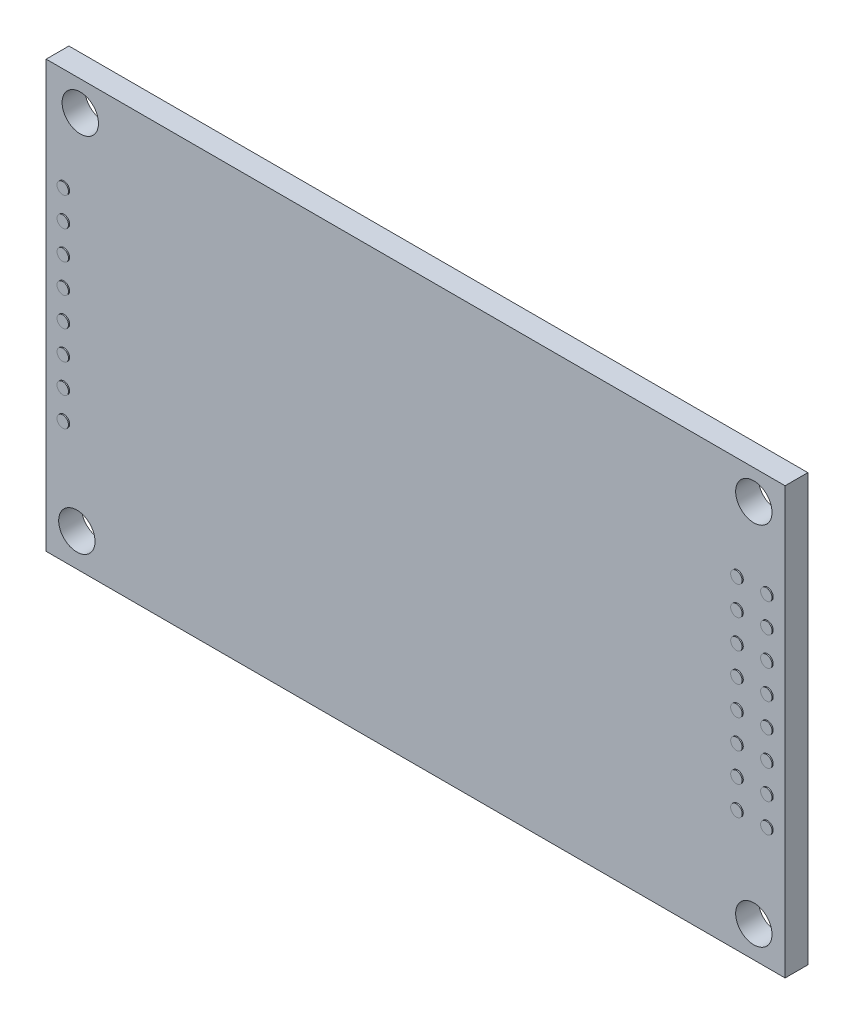
SolidWorks part; units mm, degrees
ref_plane "Front Plane" through (0, 0, 0) normal (0, 0, 1) x (1, 0, 0)
ref_plane "Top Plane" through (0, 0, 0) normal (0, 1, 0) x (1, 0, 0)
ref_plane "Right Plane" through (0, 0, 0) normal (1, 0, 0) x (0, 0, -1)
sketch "Sketch2" plane through (0, 0, 0) normal (0, 0, 1) x (1, 0, 0)
  line L0 (-14.3593, -99.8666) -> (81.7886, -99.8666) construction
  line L1 (-31.6794, 1.1684) -> (33.3206, 1.1684)
  line L2 (-31.6794, 1.1684) -> (-31.6794, -36.3316)
  line L3 (-31.6794, -36.3316) -> (33.3206, -36.3316)
  line L4 (33.3206, 1.1684) -> (33.3206, -36.3316)
  line L5 (29.1372, -7.8316) -> (31.7706, -7.8316) construction
  line L6 (30.4539, -7.8316) -> (30.4539, -12.2992) construction
  line L7 (31.7706, -7.8316) -> (-30.1214, -7.8316) construction
  line L8 (0.8246, -7.8316) -> (0.8246, -16.4982) construction
  circle A0 centre (30.5706, -1.4316) radius 1.6
  circle A2 centre (30.5706, -33.5816) radius 1.6
  circle A3 centre (-28.6794, -1.4316) radius 1.6
  circle A4 centre (-28.9794, -33.4316) radius 1.6
  circle A5 centre (31.7706, -7.8316) radius 0.505
  circle A6 centre (29.1372, -7.8316) radius 0.2013
  dimension "D1" = 3.2
  dimension "D2" = 1.01
  dimension "D9" = 3.2
  dimension "D12" = 3.2
  dimension "D15" = 3.2
  dimension "D3" = 2.75
  dimension "D4" = 2.6
  dimension "D5" = 37.5
  dimension "D6" = 65
  dimension "D7" = 1.1684
  dimension "D8" = 33.3206
  dimension "D10" = 2.75
  dimension "D11" = 2.75
  dimension "D13" = 2.6
  dimension "D14" = 3
  dimension "D16" = 2.7
  dimension "D17" = 2.9
  dimension "D18" = 1.55
  dimension "D19" = 9
extrude "Boss-Extrude1" add sketch "Sketch2" against normal blind 2 contours A5 | L4 L1 L2 L3 A5 A4 A3 A2 A0 region at (0.8082, -17.5868, 0) region at (31.7706, -7.8316, 0)
extrude "Boss-Extrude2" add sketch "Sketch2<3>" along normal blind 0.1 contours A5
sketch "Sketch2<3>" plane through (0, 0, 0) normal (0, 0, 1) x (1, 0, 0) same geometry as "Sketch2"
pattern_linear "LPattern1" count 8 spacing 2.54 along (0, -1, 0) of "Boss-Extrude2"
ref_plane "Plane1" through (30.4539, 0, 0) normal (1, 0, 0) x (0, 0, -1)
mirror "Mirror1" about plane through (30.4539, 0, 0) normal (1, 0, 0) of "LPattern1", "Boss-Extrude2"
ref_plane "Plane2" through (0.8246, 0, 0) normal (1, 0, 0) x (0, 0, -1)
mirror "Mirror2" about plane through (0.8246, 0, 0) normal (1, 0, 0) of "LPattern1", "Boss-Extrude2"
